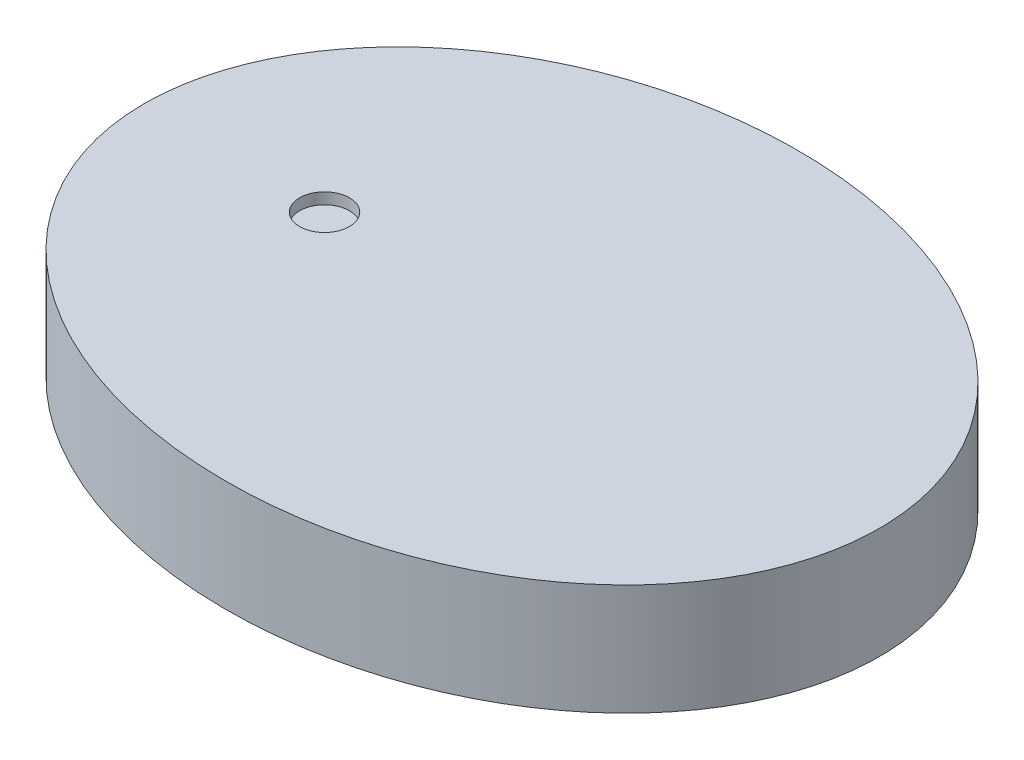
SolidWorks part; units mm, degrees
ref_plane "Front Plane" through (0, 0, 0) normal (0, 0, 1) x (1, 0, 0)
ref_plane "Top Plane" through (0, 0, 0) normal (0, 1, 0) x (1, 0, 0)
ref_plane "Right Plane" through (0, 0, 0) normal (1, 0, 0) x (0, 0, -1)
sketch "Sketch2" plane through (0, 0, 0) normal (0, 1, 0) x (1, 0, 0)
  line L1 (-14.4231, 13.5577) -> (34.5769, 13.5577)
  line L2 (-14.4231, 13.5577) -> (-14.4231, -6.4423)
  line L3 (-14.4231, -6.4423) -> (34.5769, -6.4423)
  line L4 (34.5769, 13.5577) -> (34.5769, -6.4423)
  dimension "D1" = 49
  dimension "D2" = 20
extrude "Boss-Extrude1" add sketch "Sketch2" along normal blind 10
sketch "Sketch3" plane through (0, 0, 0) normal (0, -1, 0) x (1, 0, 0)
  line L0 (34.5769, 6.4423) -> (34.5769, -13.5577) construction
  line L1 (27.5769, -5.0677) -> (-2.4231, -5.0677)
  line L2 (27.5769, -5.0677) -> (27.5769, -2.0477)
  line L3 (27.5769, -2.0477) -> (-2.4231, -2.0477)
  line L4 (-2.4231, -5.0677) -> (-2.4231, -2.0477)
  line L5 (-14.4231, -3.5577) -> (34.5769, -3.5577) construction
  line L6 (-14.4231, -13.5577) -> (-14.4231, 6.4423) construction
  dimension "D1" = 30
  dimension "D2" = 7
  dimension "D3" = 3.02
  dimension "D4" = 1.51
extrude "Cut-Extrude1" cut sketch "Sketch3" against normal blind 2
sketch "Sketch4" plane through (0, 0, 0) normal (0, -1, 0) x (1, 0, 0)
  line L0 (-2.4231, -2.0477) -> (-2.4231, -5.0677) construction
  line L1 (-2.4231, -6.5477) -> (-7.4231, -6.5477)
  line L2 (-2.4231, -6.5477) -> (-2.4231, -0.5477)
  line L3 (-2.4231, -0.5477) -> (-7.4231, -0.5477)
  line L4 (-7.4231, -6.5477) -> (-7.4231, -0.5477)
  line L6 (27.5769, -2.0477) -> (-2.4231, -2.0477) construction
  dimension "D1" = 6
  dimension "D2" = 5
  dimension "D3" = 1.5
extrude "Cut-Extrude2" cut sketch "Sketch4" against normal blind 5
sketch "Sketch5" plane through (0, 5, 0) normal (0, -1, 0) x (1, 0, 0)
  line L0 (-7.4231, -3.5477) -> (-2.4231, -3.5577) construction
  line L1 (-7.4231, -0.5477) -> (-7.4231, -6.5477) construction
  line L2 (-2.4231, -2.0477) -> (-2.4231, -5.0677) construction
  circle A0 centre (-4.9231, -3.5527) radius 7
  dimension "D1" = 14
extrude "Cut-Extrude3" cut sketch "Sketch5" against normal through all
sketch "Sketch12" plane through (0, 0, 0) normal (0, -1, 0) x (1, 0, 0)
  line L1 (-7.4231, -0.5477) -> (-2.4231, -0.5477)
  line L2 (-7.4231, -0.5477) -> (-7.4231, -6.5477)
  line L3 (-7.4231, -6.5477) -> (-2.4231, -6.5477)
  line L4 (-2.4231, -0.5477) -> (-2.4231, -6.5477)
extrude "Boss-Extrude4" add sketch "Sketch12" against normal blind 0.8
sketch "Sketch14" plane through (0, 0, 6.4423) normal (0, 0, 1) x (1, 0, 0)
  line L0 (-14.4231, 10) -> (34.5769, 10) construction
  line L1 (5.0769, 10) -> (34.5769, 10)
  line L2 (5.0769, 10) -> (5.0769, 4)
  line L3 (5.0769, 4) -> (34.5769, 4)
  line L4 (34.5769, 10) -> (34.5769, 4)
  line L5 (34.5769, 10) -> (34.5769, 0) construction
  line L6 (27.5769, 2) -> (-2.4231, 2) construction
  line L7 (2.0769, 5) -> (2.0769, 10) construction
  dimension "D1" = 2
  dimension "D2" = 3
extrude "Cut-Extrude6" cut sketch "Sketch14" against normal through all
sketch "Sketch20" plane through (0, 0.8, 0) normal (0, 1, 0) x (1, 0, 0)
  line L0 (-2.4231, 0.5477) -> (-7.4231, 0.5477) construction
  line L1 (-7.4231, 6.5477) -> (-2.4231, 6.5477)
  line L2 (-7.4231, 6.5477) -> (-7.4231, 0.5477)
  line L3 (-7.4231, 0.5477) -> (-2.4231, 0.5477)
  line L4 (-2.4231, 6.5477) -> (-2.4231, 0.5477)
  line L5 (-2.4231, 0.5477) -> (-7.4231, 0.5477) construction
extrude "Boss-Extrude6" add sketch "Sketch20" along normal up to surface (4.2 mm away) up to face at (-4.9231, 5, -10.5527)
sketch "Sketch21" plane through (0, 5, 0) normal (0, 1, 0) x (1, 0, 0)
  circle A0 centre (-4.9231, 3.5527) radius 4.6
  dimension "D1" = 9.2
extrude "Cut-Extrude8" cut sketch "Sketch21" against normal blind 0.5
sketch "Sketch22" plane through (0, 4.5, 0) normal (0, 1, 0) x (1, 0, 0)
  circle A0 centre (-4.9231, 3.5527) radius 3.825
  dimension "D1" = 7.65
extrude "Cut-Extrude9" cut sketch "Sketch22" against normal blind 4
sketch "Sketch24" plane through (0, 5, 0) normal (0, 1, 0) x (1, 0, 0)
  circle A0 centre (-4.9231, 3.5527) radius 4.25
  circle A1 centre (-4.9231, 3.5527) radius 4.6
  dimension "D1" = 9.2
  dimension "D2" = 8.5
extrude "Cut-Extrude11" cut sketch "Sketch24" against normal blind 1
sketch "Sketch26" plane through (0, 4.5, 0) normal (0, 1, 0) x (1, 0, 0)
  circle A0 centre (-4.9231, 3.5527) radius 3.825
  circle A1 centre (-4.9231, 3.5527) radius 5.0656
extrude "Boss-Extrude9" add sketch "Sketch26" along normal blind 8
sketch "Sketch27" plane through (0, 5, 0) normal (0, 1, 0) x (1, 0, 0)
  circle A0 centre (-4.9231, 3.5527) radius 4.6
  circle A1 centre (-4.9231, 3.5527) radius 7
extrude "Cut-Extrude12" cut sketch "Sketch27" against normal blind 1
sketch "Sketch39" plane through (0, 4, 0) normal (0, 1, 0) x (1, 0, 0)
  line L0 (5.0769, 3.5577) -> (29.0295, 3.5577) construction
  line L1 (5.0769, 13.5577) -> (5.0769, -6.4423) construction
  line L4 (6.3269, -0.6923) -> (6.3269, 8.9673) construction
  line L5 (5.0769, 13.5577) -> (5.0769, -6.4423) construction
  circle A0 centre (6.3269, -0.6923) radius 0.6
  circle A1 centre (7.5769, 7.8077) radius 0.6
  circle A2 centre (9.9936, 7.8077) radius 0.6
  circle A3 centre (8.7436, -0.6923) radius 0.6
  circle A4 centre (12.4103, 7.8077) radius 0.6
  circle A5 centre (11.1603, -0.6923) radius 0.6
  circle A6 centre (14.8269, 7.8077) radius 0.6
  circle A7 centre (13.5769, -0.6923) radius 0.6
  circle A8 centre (17.2436, 7.8077) radius 0.6
  circle A9 centre (15.9936, -0.6923) radius 0.6
  circle A10 centre (19.6603, 7.8077) radius 0.6
  circle A11 centre (18.4103, -0.6923) radius 0.6
  circle A12 centre (22.0769, 7.8077) radius 0.6
  circle A13 centre (20.8269, -0.6923) radius 0.6
  circle A22 centre (24.4936, 7.8077) radius 0.6 [skipped]
  circle A23 centre (23.2436, -0.6923) radius 0.6 [skipped]
  dimension "D1" = 1.2
  dimension "D2" = 1.2
  dimension "D7" = 1.25
  dimension "D3" = 8.5
  dimension "D4" = 1.25
  dimension "D5" = 4.25
  dimension "D6" = 8
fillet "Fillet1" radius 0.5 1 edges at (5.0769, 4, -3.5577)
sketch "Sketch56" plane through (0, 0, 0) normal (0, -1, 0) x (1, 0, 0)
  line L0 (27.5769, -2.0477) -> (-2.4231, -2.0477) construction
  line L1 (-2.4231, -5.0677) -> (-2.4231, -2.0477) construction
  circle A0 centre (28.9269, -3.5577) radius 2
  dimension "D1" = 4
  dimension "D2" = 1.51
  dimension "D3" = 31.35
extrude "Cut-Extrude13" cut sketch "Sketch56" against normal up to surface (2 mm away) up to face at (13.1618, 2, -3.5578)
sketch "Sketch57" plane through (0, 4, 0) normal (0, 1, 0) x (1, 0, 0)
  line L0 (26.0569, 11.0577) -> (26.0569, -3.9423) construction
  line L1 (24.4319, 0.5577) -> (21.4319, 0.5577)
  line L2 (30.6819, 0.5577) -> (27.6819, 0.5577)
  line L3 (30.6819, 0.5577) -> (30.6819, 6.5577)
  line L4 (30.6819, 6.5577) -> (27.6819, 6.5577)
  line L5 (27.6819, 0.5577) -> (27.6819, 6.5577)
  line L6 (30.6819, 0.5577) -> (27.6819, 6.5577) construction
  line L7 (30.6819, 6.5577) -> (27.6819, 0.5577) construction
  line L8 (24.4319, 0.5577) -> (24.4319, 6.5577)
  line L9 (24.4319, 6.5577) -> (21.4319, 6.5577)
  line L10 (21.4319, 0.5577) -> (21.4319, 6.5577)
  line L11 (24.4319, 0.5577) -> (21.4319, 6.5577) construction
  line L12 (24.4319, 6.5577) -> (21.4319, 0.5577) construction
  line L13 (5.5769, 13.5577) -> (5.5769, -6.4423) construction
  line L14 (5.5769, 13.5577) -> (34.5769, 13.5577) construction
  circle A1 centre (26.0569, 3.5577) radius 6
  circle A2 centre (26.0569, 3.5577) radius 5.8
  point P6 (26.0569, 3.5577)
  point P7 (29.1819, 3.5577)
  point P19 (22.9319, 3.5577)
  dimension "D1" = 11.6
  dimension "D2" = 0.2
  dimension "D3" = 15
  dimension "D4" = 3
  dimension "D11" = 20.48
  dimension "D5" = 6
  dimension "D6" = 3.125
  dimension "D7" = 3.125
  dimension "D8" = 6
  dimension "D9" = 3
  dimension "D10" = 20.48
  dimension "D12" = 10
extrude "Boss-Extrude19" add sketch "Sketch57" along normal blind 5.3 contours L5 L2 L3 L4 | L10 L1 L8 L9 region at (22.9319, 4, -3.5577) region at (29.1819, 4, -3.5577)
sketch "Sketch58" plane through (30.6819, 0, 0) normal (1, 0, 0) x (0, 0, -1)
  line L2 (0.5577, 4) -> (6.5577, 4) construction
  line L3 (0.5577, 9.3) -> (0.5577, 4) construction
  circle A0 centre (3.5577, 7) radius 1.5
  dimension "D1" = 3
  dimension "D2" = 3
  dimension "D3" = 3
extrude "Cut-Extrude14" cut sketch "Sketch58" against normal up to surface (9.25 mm away) up to face at (21.4319, 6.65, -3.5577)
fillet "Fillet2" radius 0.3 2 edges at (24.4319, 9.3, -3.5577) (27.6819, 9.3, -3.5577)
fillet "Fillet3" radius 0.8 10 edges at (21.4319, 6.65, -0.5577) (21.4319, 6.65, -6.5577) (21.4319, 4, -3.5577) (22.9319, 4, -6.5577) (30.6819, 6.65, -6.5577) (29.1819, 4, -6.5577) (30.6819, 6.65, -0.5577) (30.6819, 4, -3.5577) (29.1819, 4, -0.5577) (22.9319, 4, -0.5577)
ref_plane "Plane1" through (0, 0, -3.5577) normal (0, 0, -1) x (-1, 0, 0)
sketch "Sketch60" plane through (0, 0, -13.5577) normal (0, 0, -1) x (-1, 0, 0)
  line L1 (-34.5769, 4) -> (-15.5769, 4)
  line L2 (-34.5769, 4) -> (-34.5769, 0)
  line L3 (-34.5769, 0) -> (-15.5769, 0)
  line L4 (-15.5769, 4) -> (-15.5769, 0)
  line L5 (-34.5769, 0) -> (14.4231, 0) construction
  dimension "D1" = 19
extrude "Boss-Extrude21" add sketch "Sketch60" along normal blind 1
sketch "Sketch59" plane through (0, 0, -14.5577) normal (0, 0, -1) x (-1, 0, 0)
  line L0 (-15.5769, 0) -> (14.4231, 0) construction
  line L1 (-38.3869, -3) -> (-15.5269, -3)
  line L2 (-38.3869, -3) -> (-38.3869, 10)
  line L3 (-38.3869, 10) -> (-15.5269, 10)
  line L4 (-15.5269, -3) -> (-15.5269, 10)
  line L5 (-34.5769, 4) -> (-34.5769, 0) construction
  dimension "D1" = 22.86
  dimension "D2" = 13
  dimension "D3" = 3
  dimension "D4" = 3.81
extrude "Boss-Extrude20" add sketch "Sketch59" along normal blind 11
ref_axis "Axis1" through (28.9269, 2, -3.5577) along (0, -1, 0)
mirror "Mirror4" about plane through (0, 0, -3.5577) normal (0, 0, -1) of "Boss-Extrude20", "Boss-Extrude21"
sketch "Sketch61" plane through (0, 10, 0) normal (0, 1, 0) x (1, 0, 0)
  line L0 (24.4319, 7.3577) -> (24.4319, 20.2077) construction
  line L1 (-14.4231, 3.5577) -> (34.5769, 3.5577) construction
  line L2 (-14.4231, 13.5577) -> (-14.4231, -6.4423) construction
  line L3 (34.5769, 14.5577) -> (34.5769, -7.4423) construction
  line L4 (24.4319, 20.2077) -> (20.4069, 20.2077) construction
  line L5 (27.6819, 7.3577) -> (27.6819, 20.2077) construction
  line L6 (27.6819, 20.2077) -> (31.7069, 20.2077) construction
  line L7 (27.6819, -13.0923) -> (31.7069, -13.0923) construction
  line L8 (27.6819, -0.2423) -> (27.6819, -13.0923) construction
  line L9 (24.4319, -13.0923) -> (20.4069, -13.0923) construction
  line L10 (24.4319, -0.2423) -> (24.4319, -13.0923) construction
  circle A0 centre (20.4069, 20.2077) radius 2.5
  circle A1 centre (31.7069, 20.2077) radius 2.5
  circle A2 centre (31.7069, -13.0923) radius 2.5
  circle A3 centre (20.4069, -13.0923) radius 2.5
  dimension "D3" = 5
  dimension "D2" = 11.3
  dimension "D4" = 16.65
extrude "Cut-Extrude15" cut sketch "Sketch61" against normal up to next
fillet "Fillet4" radius 4 8 edges at (38.3869, 3.5, -25.5577) (15.5269, 3.5, -25.5577) (38.3869, 3.5, -14.5577) (38.3869, 3.5, 7.4423) (38.3869, 3.5, 18.4423) (15.5269, 3.5, 18.4423) (-14.4231, 5, 6.4423) (-14.4231, 5, -13.5577)
sketch "Sketch63" plane through (0, 4, 0) normal (0, 1, 0) x (-1, 0, 0)
  ellipse E0 centre (-14.0191, -3.6347) end of major axis (23.7699, -3.6347) minor radius 29.4175
  point P1 (-119.2286, 53.0861)
extrude "Boss-Extrude23" add sketch "Sketch63" along normal blind 11.3975 and the other way blind 0.0161 separate body contours E0
combine bodies "Combine1" operation type subtract main body 195 bodies to subtract 193
sketch "Sketch66" plane through (0, 15.3975, 0) normal (0, 1, 0) x (1, 0, 0)
  circle A0 centre (-4.8443, 3.2347) radius 2.5606
  point P2 (0, 0)
  point P3 (-4.9776, 3.6347)
  point P4 (0, 0)
  point P5 (0, 0)
  point P6 (-4.8443, 3.2347)
extrude "Cut-Extrude16" cut sketch "Sketch66" against normal blind 1.154
